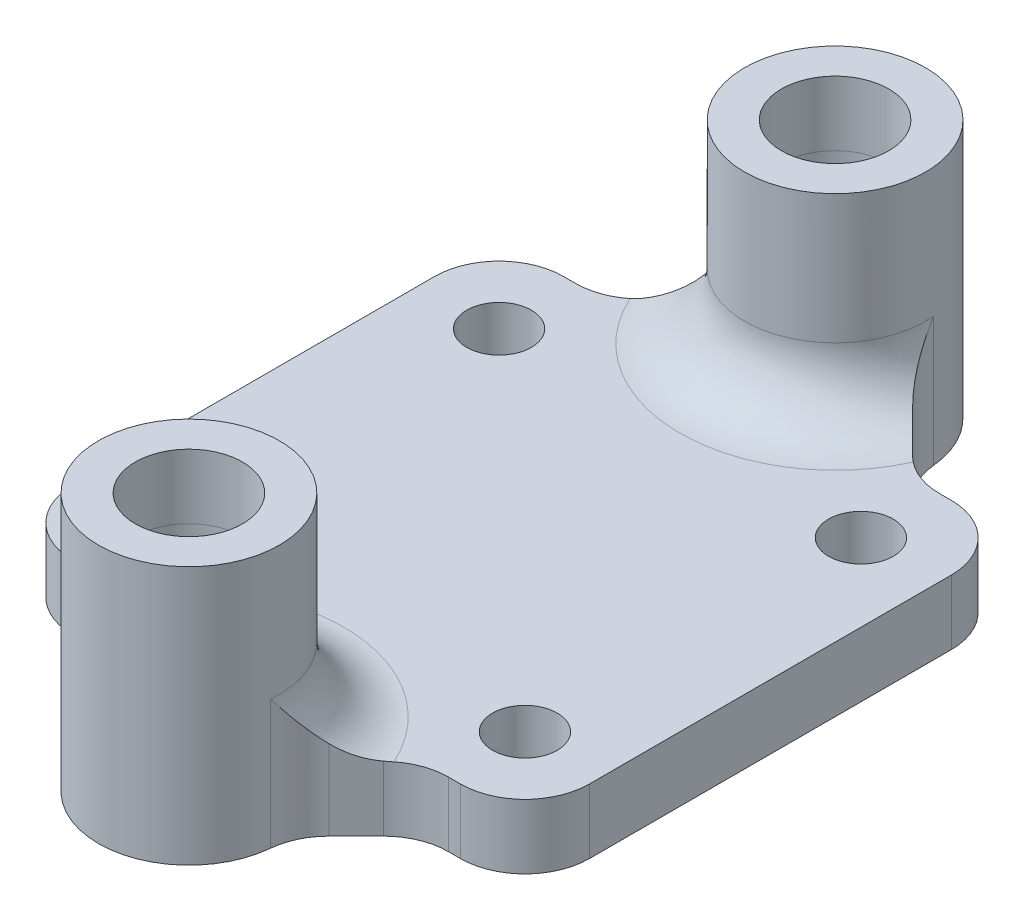
SolidWorks part; units mm, degrees
ref_plane "Front Plane" through (0, 0, 0) normal (0, 0, 1) x (1, 0, 0)
ref_plane "Top Plane" through (0, 0, 0) normal (0, 1, 0) x (1, 0, 0)
ref_plane "Right Plane" through (0, 0, 0) normal (1, 0, 0) x (0, 0, -1)
sketch "Sketch1" plane through (0, 0, 0) normal (0, 1, 0) x (1, 0, 0)
  line L1 (14, -13) -> (-14, -13) construction
  line L2 (14, -13) -> (14, 13) construction
  line L3 (14, 13) -> (-14, 13) construction
  line L4 (-14, -13) -> (-14, 13) construction
  line L5 (14, -13) -> (-14, 13) construction
  line L6 (14, 13) -> (-14, -13) construction
  line L7 (20, -19) -> (-20, -19)
  line L8 (20, -19) -> (20, 19)
  line L9 (20, 19) -> (-20, 19)
  line L10 (-20, -19) -> (-20, 19)
  line L11 (20, -19) -> (-20, 19) construction
  line L12 (20, 19) -> (-20, -19) construction
  circle A0 centre (14, 13) radius 2.5
  circle A1 centre (14, -13) radius 2.5
  circle A2 centre (-14, -13) radius 2.5
  circle A3 centre (-14, 13) radius 2.5
  point P0 (0, 0)
  point P6 (0, 0)
  dimension "D5" = 5
  dimension "D1" = 26
  dimension "D2" = 28
  dimension "D3" = 6
  dimension "D4" = 6
extrude "Boss-Extrude1" add sketch "Sketch1" along normal blind 5
sketch "Sketch2" plane through (0, 0, 0) normal (0, 1, 0) x (1, 0, 0)
  line L0 (0, 25) -> (0, -25) construction
  circle A0 centre (0, 25) radius 4.15
  circle A1 centre (0, -25) radius 4.15
  circle A2 centre (0, 25) radius 7
  circle A3 centre (0, -25) radius 7
  point P4 (0, 0)
  dimension "D1" = 50
  dimension "D2" = 8.3
  dimension "D3" = 14
extrude "Boss-Extrude2" add sketch "Sketch2" along normal blind 20 separate body
sketch "Sketch3" plane through (0, 0, 0) normal (0, 1, 0) x (1, 0, 0)
  line L0 (-7, 25) -> (-7, -25)
  line L1 (7, 25) -> (7, -25)
  arc A0 (7, 25) -> (-7, 25) centre (0, 25) ccw
  arc A1 (-7, -25) -> (7, -25) centre (0, -25) ccw
  circle A2 centre (0, 25) radius 7 construction
extrude "Boss-Extrude4" add sketch "Sketch3" along normal up to surface (5 mm away) up to face at (-14, 5, 15.5)
chamfer "Chamfer2" distance 10 angle 1 2 edges at (0, 5, 29.15) (0, 5, -20.85) first distance on face at (0, 5, 29.15) first distance on face at (0, 5, -20.85)
fillet "Fillet2" radius 5 6 edges at (20, 2.5, 19) (20, 2.5, -19) (-20, 2.5, 19) (-20, 2.5, -19) (0, 5, 18) (0, 5, -18)
chamfer "Chamfer3" distance 5 angle 45 4 edges at (-7, 2.9222, -19) (7, 2.9222, -19) (7, 2.9222, 19) (-7, 2.9222, 19)
fillet "Fillet3" radius 5 8 edges at (-12, 2.5, -19) (-7, 4.58, -24) (7, 4.58, -24) (12, 2.5, -19) (12, 2.5, 19) (7, 4.58, 24) (-12, 2.5, 19) (-7, 4.58, 24)
